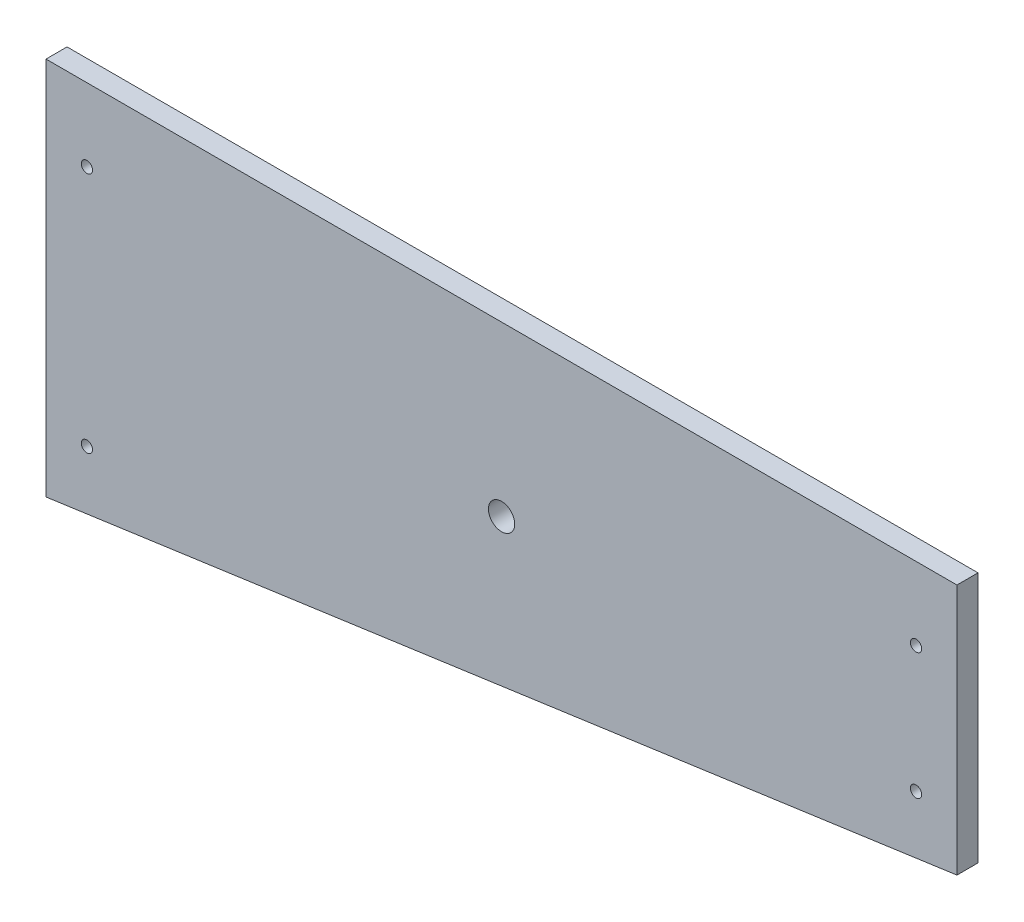
SolidWorks part; units mm, degrees
material "Acrylic (Medium-high impact)"
ref_plane "Front Plane" through (0, 0, 0) normal (0, 0, 1) x (1, 0, 0)
ref_plane "Top Plane" through (0, 0, 0) normal (0, 1, 0) x (1, 0, 0)
ref_plane "Right Plane" through (0, 0, 0) normal (1, 0, 0) x (0, 0, -1)
sketch "Sketch1" plane through (0, 0, 0) normal (0, 0, 1) x (1, 0, 0)
  line L1 (274.7772, 114.4016) -> (0, 114.4016)
  line L2 (274.7772, 114.4016) -> (274.7772, 0)
  line L3 (274.7772, 0) -> (0, 0)
  line L4 (0, 114.4016) -> (0, 0)
  line L5 (274.7772, 114.4016) -> (0, 0) construction
  line L6 (274.7772, 0) -> (0, 114.4016) construction
  point P0 (137.3886, 57.2008)
  dimension "D1" = 114.4016
  dimension "D2" = 274.7772
extrude "Boss-Extrude1" add sketch "Sketch1" along normal blind 6.35
hole_wizard "M3 Clearance Hole1" positions "Sketch2" profile "Sketch3" hole size "M3" standard "ANSI Metric" end condition through all
sketch "Sketch2" plane through (0, 0, 6.35) normal (0, 0, 1) x (1, 0, 0)
  line L0 (0, 114.4016) -> (0, 0) construction
  line L1 (274.7772, 114.4016) -> (0, 114.4016) construction
  line L2 (274.7772, 0) -> (274.7772, 114.4016) construction
  point P0 (12.3444, 92.4052)
  point P2 (12.3444, 19.3802)
  point P4 (262.4328, 54.3052)
  point P6 (262.4328, 92.4052)
  dimension "D1" = 12.3444
  dimension "D2" = 21.9964
  dimension "D3" = 12.3444
  dimension "D4" = 73.025
  dimension "D5" = 38.1
sketch "Sketch3" plane through (12.3444, 92.4052, 6.35) normal (1, 0, 0) x (0, -1, 0)
  line L0 (0, 0) -> (0, 6.35)
  line L1 (0, 6.35) -> (1.7, 6.35)
  line L2 (1.7, 6.35) -> (1.7, 0)
  line L5 (1.7, 0) -> (0, 0)
  line L11 (0, -6.35) -> (0, 107.95) construction
  dimension "Thru Hole Dia." = 3.4
  dimension "Thru Hole Depth" = 6.35
sketch "Sketch4" plane through (0, 0, 6.35) normal (0, 0, 1) x (1, 0, 0)
  line L0 (0, 114.4016) -> (0, 0) construction
  line L1 (46.99, 95.3516) -> (50.4952, 95.3516)
  line L2 (46.99, 95.3516) -> (46.99, 19.1516)
  line L3 (46.99, 19.1516) -> (50.4952, 19.1516)
  line L4 (50.4952, 95.3516) -> (50.4952, 19.1516)
  line L5 (224.282, 95.3516) -> (227.7872, 95.3516)
  line L6 (224.282, 95.3516) -> (224.282, 19.1516)
  line L7 (224.282, 19.1516) -> (227.7872, 19.1516)
  line L8 (227.7872, 95.3516) -> (227.7872, 19.1516)
  line L9 (274.7772, 0) -> (274.7772, 114.4016) construction
  line L10 (274.7772, 114.4016) -> (0, 114.4016) construction
  dimension "D1" = 3.5052
  dimension "D2" = 76.2
  dimension "D3" = 46.99
  dimension "D4" = 46.99
  dimension "D5" = 19.05
extrude "Cut-Extrude1" [suppressed] cut sketch "Sketch4" against normal through all
sketch "Sketch5" plane through (0, 0, 6.35) normal (0, 0, 1) x (1, 0, 0)
  line L0 (0, 0) -> (274.7772, 0)
  line L1 (274.7772, 0) -> (274.7772, 38.6174)
  line L2 (274.7772, 0) -> (274.7772, 114.4016) construction
  line L3 (274.7772, 38.6174) -> (0, 0)
  dimension "D1" = 8
extrude "Cut-Extrude2" cut sketch "Sketch5" against normal through all
sketch "Sketch6" plane through (0, 0, 6.35) normal (0, 0, 1) x (1, 0, 0)
  line L0 (274.7772, 114.4016) -> (0, 114.4016) construction
  line L1 (0, 114.4016) -> (0, 0) construction
  circle A0 centre (137.414, 63.6016) radius 3.9687
  point P2 (0, 0)
  dimension "D1" = 7.9375
  dimension "D2" = 50.8
  dimension "D3" = 137.414
extrude "diaphragm" cut sketch "Sketch6" against normal through all
